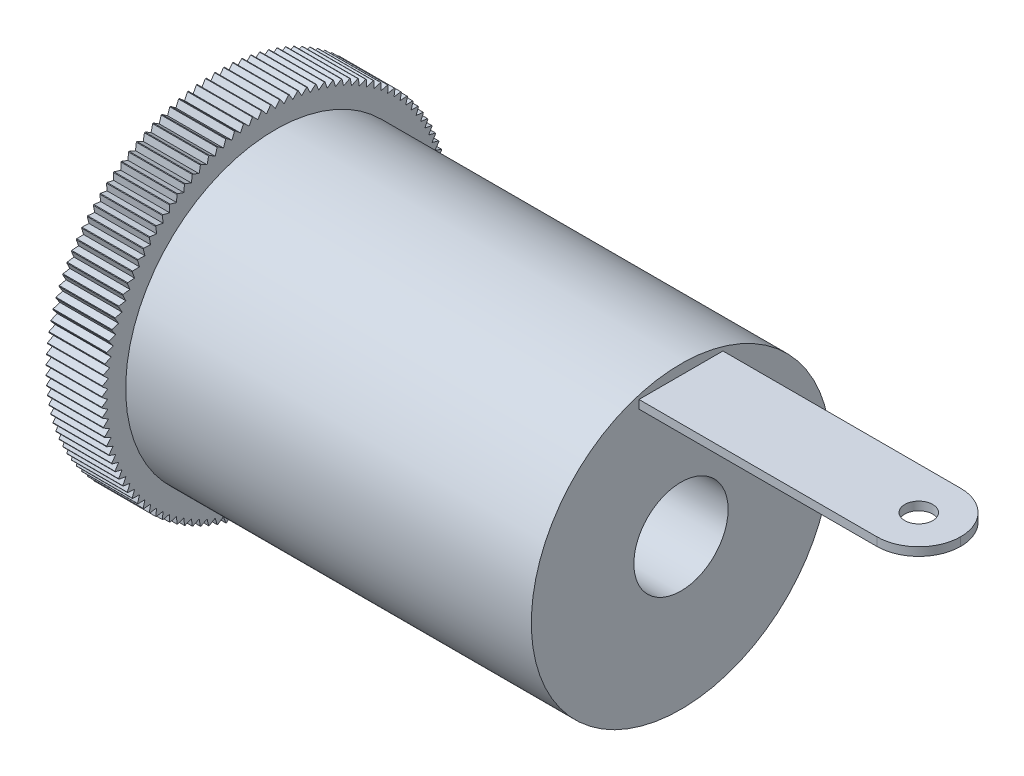
SolidWorks part; units mm, degrees
ref_plane "前视基准面" through (0, 0, 0) normal (0, 0, 1) x (1, 0, 0)
ref_plane "上视基准面" through (0, 0, 0) normal (0, 1, 0) x (1, 0, 0)
ref_plane "右视基准面" through (0, 0, 0) normal (1, 0, 0) x (0, 0, -1)
sketch "草图1" plane through (0, 0, 0) normal (0, 0, 1) x (1, 0, 0)
  line L0 (0, 0) -> (-25.3823, 0) construction
  line L1 (-12.8123, 6.2) -> (-10.8123, 6.2)
  line L2 (-10.8123, 6.2) -> (-10.8123, 5.35)
  line L3 (-10.8123, 5.35) -> (3.6877, 5.35)
  line L4 (3.6877, 5.35) -> (3.6877, 1.6848)
  line L5 (-12.8123, 6.2) -> (-12.8123, 1.6848)
  line L6 (-12.8123, 1.6848) -> (3.6877, 1.6848)
  dimension "D1" = 6.2
  dimension "D2" = 5.35
  dimension "D3" = 2
  dimension "D4" = 16.5
revolve "旋转1" add sketch "草图1" angle 360 about L0
sketch "草图2" plane through (-12.8123, 0, 0) normal (-1, 0, 0) x (0, 0, 1)
  line L0 (-0.15, 6.1982) -> (0, 6)
  line L1 (0, 6) -> (0.15, 6.1982)
  line L2 (0, 0) -> (0, 9.9175) construction
  circle A0 centre (0, 0) radius 6.2 construction
  circle A2 centre (0, 0) radius 6.2
  arc A3 (0.15, 6.1982) -> (-0.15, 6.1982) centre (0, 0) ccw
  dimension "D1" = 6
  dimension "D2" = 0.3
  dimension "D3" = 0
extrude "切除-拉伸1" cut sketch "草图2" against normal blind 10
pattern_circular "阵列(圆周)1" count 120 every 3 about axis through (0, 0, 0) along (1, 0, 0) of "切除-拉伸1"
sketch "草图3" plane through (3.6877, 0, 0) normal (1, 0, 0) x (0, 0, -1)
  line L0 (0, 5.35) -> (0, -0.6791) construction
  line L1 (-1.5, 4.9952) -> (1.5, 4.9952)
  line L2 (-1.5, 4.9952) -> (-1.5, 4.6952)
  line L3 (-1.5, 4.6952) -> (1.5, 4.6952)
  line L4 (1.5, 4.9952) -> (1.5, 4.6952)
  circle A0 centre (0, 0) radius 5.35 construction
  circle A1 centre (0, 0) radius 5.35 construction
  dimension "D1" = 0.3
  dimension "D2" = 3
extrude "凸台-拉伸1" add sketch "草图3" along normal blind 10
fillet "圆角2" radius 1.5 2 edges at (13.6877, 4.8452, -1.5) (13.6877, 4.8452, 1.5)
sketch "草图4" plane through (0, 4.9952, 0) normal (0, 1, 0) x (1, 0, 0)
  circle A0 centre (12.1877, 0) radius 0.5
  dimension "D1" = 1
extrude "切除-拉伸2" cut sketch "草图4" against normal blind 11
